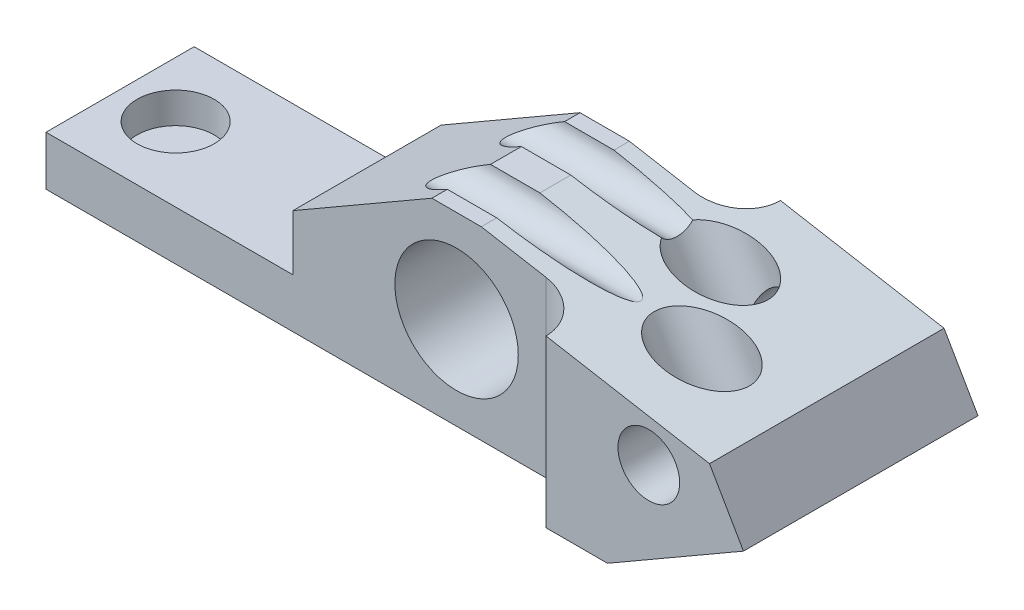
SolidWorks part; units mm, degrees
ref_plane "Front Plane" through (0, 0, 0) normal (0, 0, 1) x (1, 0, 0)
ref_plane "Top Plane" through (0, 0, 0) normal (0, 1, 0) x (1, 0, 0)
ref_plane "Right Plane" through (0, 0, 0) normal (1, 0, 0) x (0, 0, -1)
sketch "Sketch1" plane through (0, 0, 0) normal (0, 0, 1) x (1, 0, 0)
  line L13 (49.4833, 12.7183) -> (43.9833, 22.2446)
  line L15 (0, 30) -> (-8, 30)
  line L16 (-8, 30) -> (-30.5167, 17)
  line L17 (-30.5167, 17) -> (-30.5167, 8)
  line L19 (-70.5167, 8) -> (-70.5167, 0)
  line L21 (0, 0) -> (-30.5167, 0)
  line L22 (-30.5167, 0) -> (-70.5167, 0)
  line L24 (49.4833, 12.7183) -> (27.4546, 0)
  line L25 (27.4546, 0) -> (0, 0)
  line L29 (-70.5167, 8) -> (-30.5167, 8)
  line L30 (-30.5167, 8) -> (-30.5167, 0)
  line L31 (43.9833, 22.2446) -> (0, 30)
  circle A0 centre (-4, 15) radius 10
  point P5 (-4, 30)
  dimension "D10" = 10
  dimension "D12" = 20
  dimension "D1" = 11
  dimension "D2" = 30
  dimension "D3" = 120
  dimension "D4" = 40
  dimension "D5" = 30
  dimension "D6" = 4
  dimension "D7" = 30
  dimension "D8" = 8
  dimension "D9" = 9
  dimension "D11" = 15
extrude "Boss-Extrude1" add sketch "Sketch1" along normal mid plane 24 contours L13 L31 L15 L16 L17 L30 L21 L25 L24 A0 | L30 L29 L19 L22 region at (8.4863, 13.2357, 0) region at (-50.5167, 4, 0)
sketch "Sketch2" plane through (0, 0, 0) normal (0, 0, 1) x (1, 0, 0)
  line L0 (17.4833, 26.9172) -> (17.4833, 0)
  line L1 (-70.5167, 8) -> (-70.5167, 0) construction
  line L9 (49.4833, 12.7183) -> (43.9833, 22.2446)
  line L10 (43.9833, 22.2446) -> (0, 30)
  line L11 (0, 30) -> (-8, 30)
  line L12 (-8, 30) -> (-30.5167, 17)
  line L13 (-30.5167, 17) -> (-30.5167, 8)
  line L14 (-30.5167, 8) -> (-70.5167, 8)
  line L15 (-70.5167, 8) -> (-70.5167, 0)
  line L16 (-70.5167, 0) -> (27.4546, 0)
  line L17 (27.4546, 0) -> (49.4833, 12.7183)
  line L18 (49.4833, 12.7183) -> (43.9833, 22.2446)
  line L19 (43.9833, 22.2446) -> (17.4833, 26.9172)
  line L25 (17.4833, 0) -> (27.4546, 0)
  line L26 (27.4546, 0) -> (49.4833, 12.7183)
  dimension "D2" = 88
  dimension "D1" = 0
extrude "Boss-Extrude2" add sketch "Sketch2" along normal mid plane 38
ref_plane "Plane1" through (1.3637, -2.3619, 0) normal (0.5, -0.866, 0) x (-0.866, -0.5, 0)
sketch "Sketch4" plane through (1.3637, -2.3619, 0) normal (0.5, -0.866, 0) x (-0.866, -0.5, 0)
  line L0 (-49.1372, 11.4839) -> (-49.1372, 4.4805)
  line L1 (0, 0) -> (-62.1553, 0) construction
  circle A0 centre (-31.1372, 6) radius 6
  circle A1 centre (-38.1372, -6) radius 6
  dimension "D2" = 12
  dimension "D3" = 12
  dimension "D1" = 18
  dimension "D4" = 12
  dimension "D5" = 11
extrude "Cut-Extrude1" cut sketch "Sketch4" against normal blind 38 and the other way blind 38 contours A0 | A1 region at (28.3293, 13.2067, -6) region at (34.3915, 16.7067, 6)
fillet "Fillet1" radius 7 2 edges at (17.4833, 13.4586, 12) (17.4833, 13.4586, -12)
sketch "Sketch6" plane through (0, 8, 0) normal (0, 1, 0) x (1, 0, 0)
  line L0 (-70.5167, -12) -> (-70.5167, 12) construction
  line L1 (-70.5167, -12) -> (-30.5167, -12) construction
  circle A0 centre (-61.5167, 0) radius 6.25
  dimension "D1" = 12.5
  dimension "D2" = 9
  dimension "D3" = 12
extrude "Cut-Extrude2" cut sketch "Sketch6" against normal blind 5
sketch "Sketch8" plane through (0, 0, 0) normal (1, 0, 0) x (0, 0, -1)
  line L0 (0, 0) -> (0, 20.1544) construction
  line L1 (-12, 30) -> (12, 30) construction
  line L4 (-9.5, 30) -> (-2.5, 30)
  line L5 (2.5, 30) -> (9.5, 30)
  arc A0 (-9.5, 30) -> (-2.5, 30) centre (-6, 30) ccw
  arc A1 (2.5, 30) -> (9.5, 30) centre (6, 30) ccw
  dimension "D1" = 3.5
  dimension "D2" = 3.5
  dimension "D3" = 12
  dimension "D4" = 2.5
extrude "Cut-Extrude3" cut sketch "Sketch8" against normal blind 21 and the other way blind 56 contours L4 A0 | L5 A1
sketch "Sketch9" plane through (0, 0, 19) normal (0, 0, 1) x (1, 0, 0)
  line L12 (39.8915, 7.1804) -> (32.262, 20.3951) construction
  circle A0 centre (34.1481, 17.1282) radius 5
  point P2 (35.2751, 16.5159)
  point P3 (0, 0)
  point P4 (29.5386, 15.8569)
  point P5 (31.1129, 16.2824)
  point P6 (0, 0)
  point P7 (31.4869, 15.9676)
  point P8 (0, 0)
  point P9 (0, 0)
  point P10 (0, 0)
  point P12 (0, 0)
  point P14 (0, 0)
  point P15 (0, 0)
  point P16 (28.2699, 13.3096)
  point P17 (26.6832, 16.0579)
  point P18 (0, 0)
  point P19 (33.784, 17.7588)
  point P20 (34.1481, 17.1282)
  dimension "D2" = 10
extrude "Cut-Extrude4" cut sketch "Sketch9" against normal blind 14
sketch "Sketch10" plane through (0, 0, -19) normal (0, 0, -1) x (-1, 0, 0)
  line L0 (-33.8293, 3.6804) -> (-18.462, 30.2973) construction
  circle A0 centre (-26.1205, 17.0324) radius 5
  dimension "D1" = 10
extrude "Cut-Extrude5" cut sketch "Sketch10" against normal blind 11
